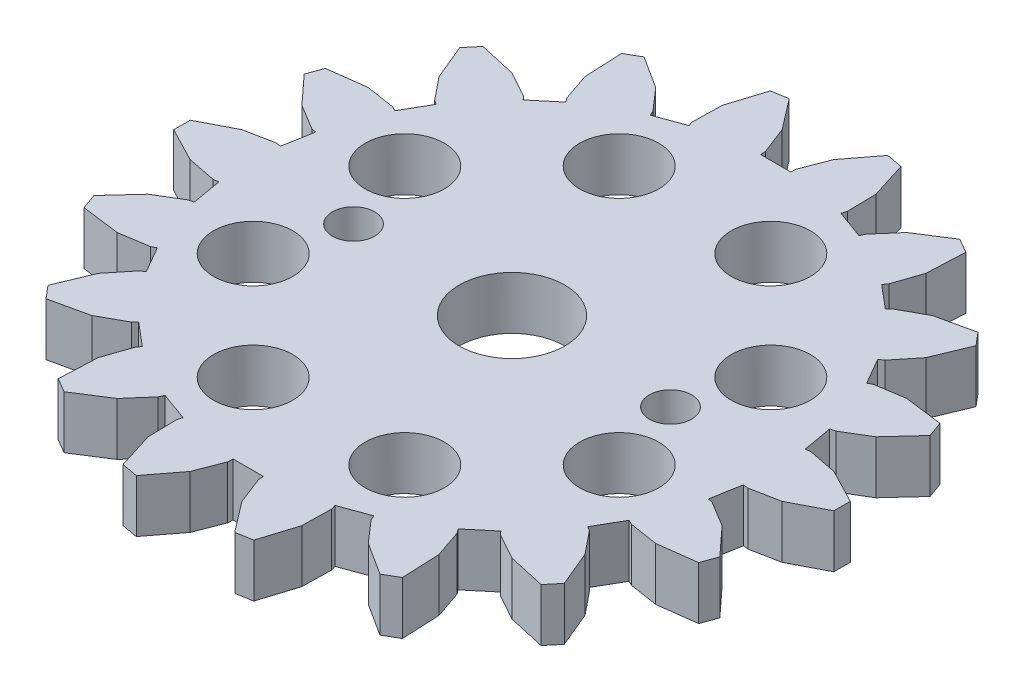
SolidWorks part; units mm, degrees
material "Acrylic (Medium-high impact)"
ref_plane "Front Plane" through (0, 0, 0) normal (0, 0, 1) x (1, 0, 0)
ref_plane "Top Plane" through (0, 0, 0) normal (0, 1, 0) x (1, 0, 0)
ref_plane "Right Plane" through (0, 0, 0) normal (1, 0, 0) x (0, 0, -1)
sketch "Sketch2" plane through (0, 0, 0) normal (0, 1, 0) x (1, 0, 0)
  line L0 (47.7625, 28.9478) -> (48.1516, 28.9935)
  line L1 (48.1516, 28.9935) -> (50.3142, 28.5692)
  line L2 (50.3142, 28.5692) -> (52.8918, 27.2307)
  line L3 (52.8918, 27.2307) -> (52.8918, 25.9859)
  line L4 (52.8918, 25.9859) -> (50.3142, 24.6474)
  line L5 (50.3142, 24.6474) -> (48.1516, 24.2231)
  line L6 (48.1516, 24.2231) -> (47.7625, 24.2688)
  line L7 (47.7625, 24.2688) -> (47.3647, 22.0134)
  line L8 (47.3647, 22.0134) -> (47.7462, 21.9233)
  line L9 (47.7462, 21.9233) -> (49.6331, 20.785)
  line L10 (49.6331, 20.785) -> (51.5977, 18.6455)
  line L11 (51.5977, 18.6455) -> (51.1718, 17.4756)
  line L12 (51.1718, 17.4756) -> (48.2916, 17.0996)
  line L13 (48.2916, 17.0996) -> (46.1145, 17.4405)
  line L14 (46.1145, 17.4405) -> (45.7645, 17.6166)
  line L15 (45.7645, 17.6166) -> (44.6194, 15.6331)
  line L16 (44.6194, 15.6331) -> (44.9469, 15.4181)
  line L17 (44.9469, 15.4181) -> (46.3307, 13.703)
  line L18 (46.3307, 13.703) -> (47.4452, 11.0207)
  line L19 (47.4452, 11.0207) -> (46.6449, 10.0669)
  line L20 (46.6449, 10.0669) -> (43.8096, 10.6987)
  line L21 (43.8096, 10.6987) -> (41.8805, 11.7635)
  line L22 (41.8805, 11.7635) -> (41.6117, 12.0488)
  line L23 (41.6117, 12.0488) -> (39.8572, 10.5766)
  line L24 (39.8572, 10.5766) -> (40.0916, 10.2624)
  line L25 (40.0916, 10.2624) -> (40.8053, 8.1776)
  line L26 (40.8053, 8.1776) -> (40.9351, 5.276)
  line L27 (40.9351, 5.276) -> (39.857, 4.6534)
  line L28 (39.857, 4.6534) -> (37.4087, 6.2167)
  line L29 (37.4087, 6.2167) -> (35.9601, 7.8772)
  line L30 (35.9601, 7.8772) -> (35.8052, 8.2373)
  line L31 (35.8052, 8.2373) -> (33.653, 7.4539)
  line L32 (33.653, 7.4539) -> (33.7657, 7.0785)
  line L33 (33.7657, 7.0785) -> (33.7233, 4.8753)
  line L34 (33.7233, 4.8753) -> (32.8529, 2.1042)
  line L35 (32.8529, 2.1042) -> (31.6267, 1.8881)
  line L36 (31.6267, 1.8881) -> (29.861, 4.1942)
  line L37 (29.861, 4.1942) -> (29.0677, 6.2501)
  line L38 (29.0677, 6.2501) -> (29.0452, 6.6414)
  line L39 (29.0452, 6.6414) -> (26.755, 6.6414)
  line L40 (26.755, 6.6414) -> (26.7324, 6.2501)
  line L41 (26.7324, 6.2501) -> (25.9392, 4.1942)
  line L42 (25.9392, 4.1942) -> (24.1734, 1.8881)
  line L43 (24.1734, 1.8881) -> (22.9472, 2.1042)
  line L44 (22.9472, 2.1042) -> (22.0768, 4.8753)
  line L45 (22.0768, 4.8753) -> (22.0344, 7.0785)
  line L46 (22.0344, 7.0785) -> (22.1471, 7.4539)
  line L47 (22.1471, 7.4539) -> (19.995, 8.2373)
  line L48 (19.995, 8.2373) -> (19.84, 7.8772)
  line L49 (19.84, 7.8772) -> (18.3914, 6.2167)
  line L50 (18.3914, 6.2167) -> (15.9432, 4.6534)
  line L51 (15.9432, 4.6534) -> (14.865, 5.276)
  line L52 (14.865, 5.276) -> (14.9948, 8.1776)
  line L53 (14.9948, 8.1776) -> (15.7085, 10.2624)
  line L54 (15.7085, 10.2624) -> (15.943, 10.5766)
  line L55 (15.943, 10.5766) -> (14.1884, 12.0488)
  line L56 (14.1884, 12.0488) -> (13.9196, 11.7635)
  line L57 (13.9196, 11.7635) -> (11.9905, 10.6987)
  line L58 (11.9905, 10.6987) -> (9.1553, 10.0669)
  line L59 (9.1553, 10.0669) -> (8.355, 11.0207)
  line L60 (8.355, 11.0207) -> (9.4694, 13.703)
  line L61 (9.4694, 13.703) -> (10.8533, 15.4181)
  line L62 (10.8533, 15.4181) -> (11.1808, 15.6331)
  line L63 (11.1808, 15.6331) -> (10.0357, 17.6166)
  line L64 (10.0357, 17.6166) -> (9.6856, 17.4405)
  line L65 (9.6856, 17.4405) -> (7.5085, 17.0996)
  line L66 (7.5085, 17.0996) -> (4.6283, 17.4756)
  line L67 (4.6283, 17.4756) -> (4.2024, 18.6455)
  line L68 (4.2024, 18.6455) -> (6.1671, 20.785)
  line L69 (6.1671, 20.785) -> (8.054, 21.9233)
  line L70 (8.054, 21.9233) -> (8.4355, 22.0134)
  line L71 (8.4355, 22.0134) -> (8.0377, 24.2688)
  line L72 (8.0377, 24.2688) -> (7.6485, 24.2231)
  line L73 (7.6485, 24.2231) -> (5.4859, 24.6474)
  line L74 (5.4859, 24.6474) -> (2.9083, 25.9859)
  line L75 (2.9083, 25.9859) -> (2.9083, 27.2307)
  line L76 (2.9083, 27.2307) -> (5.4859, 28.5692)
  line L77 (5.4859, 28.5692) -> (7.6485, 28.9935)
  line L78 (7.6485, 28.9935) -> (8.0377, 28.9478)
  line L79 (8.0377, 28.9478) -> (8.4355, 31.2032)
  line L80 (8.4355, 31.2032) -> (8.054, 31.2933)
  line L81 (8.054, 31.2933) -> (6.1671, 32.4315)
  line L82 (6.1671, 32.4315) -> (4.2024, 34.5711)
  line L83 (4.2024, 34.5711) -> (4.6283, 35.741)
  line L84 (4.6283, 35.741) -> (7.5085, 36.117)
  line L85 (7.5085, 36.117) -> (9.6856, 35.7761)
  line L86 (9.6856, 35.7761) -> (10.0357, 35.6)
  line L87 (10.0357, 35.6) -> (11.1808, 37.5835)
  line L88 (11.1808, 37.5835) -> (10.8533, 37.7985)
  line L89 (10.8533, 37.7985) -> (9.4694, 39.5136)
  line L90 (9.4694, 39.5136) -> (8.355, 42.1959)
  line L91 (8.355, 42.1959) -> (9.1553, 43.1497)
  line L92 (9.1553, 43.1497) -> (11.9905, 42.5179)
  line L93 (11.9905, 42.5179) -> (13.9196, 41.4531)
  line L94 (13.9196, 41.4531) -> (14.1884, 41.1678)
  line L95 (14.1884, 41.1678) -> (15.943, 42.64)
  line L96 (15.943, 42.64) -> (15.7085, 42.9541)
  line L97 (15.7085, 42.9541) -> (14.9948, 45.0389)
  line L98 (14.9948, 45.0389) -> (14.865, 47.9406)
  line L99 (14.865, 47.9406) -> (15.9432, 48.5632)
  line L100 (15.9432, 48.5632) -> (18.3914, 46.9999)
  line L101 (18.3914, 46.9999) -> (19.84, 45.3394)
  line L102 (19.84, 45.3394) -> (19.995, 44.9793)
  line L103 (19.995, 44.9793) -> (22.1471, 45.7627)
  line L104 (22.1471, 45.7627) -> (22.0344, 46.1381)
  line L105 (22.0344, 46.1381) -> (22.0768, 48.3413)
  line L106 (22.0768, 48.3413) -> (22.9472, 51.1123)
  line L107 (22.9472, 51.1123) -> (24.1734, 51.3285)
  line L108 (24.1734, 51.3285) -> (25.9392, 49.0224)
  line L109 (25.9392, 49.0224) -> (26.7324, 46.9665)
  line L110 (26.7324, 46.9665) -> (26.755, 46.5752)
  line L111 (26.755, 46.5752) -> (29.0452, 46.5752)
  line L112 (29.0452, 46.5752) -> (29.0677, 46.9665)
  line L113 (29.0677, 46.9665) -> (29.861, 49.0224)
  line L114 (29.861, 49.0224) -> (31.6267, 51.3285)
  line L115 (31.6267, 51.3285) -> (32.8529, 51.1123)
  line L116 (32.8529, 51.1123) -> (33.7233, 48.3413)
  line L117 (33.7233, 48.3413) -> (33.7657, 46.1381)
  line L118 (33.7657, 46.1381) -> (33.653, 45.7627)
  line L119 (33.653, 45.7627) -> (35.8052, 44.9793)
  line L120 (35.8052, 44.9793) -> (35.9601, 45.3394)
  line L121 (35.9601, 45.3394) -> (37.4087, 46.9999)
  line L122 (37.4087, 46.9999) -> (39.857, 48.5632)
  line L123 (39.857, 48.5632) -> (40.9351, 47.9406)
  line L124 (40.9351, 47.9406) -> (40.8053, 45.0389)
  line L125 (40.8053, 45.0389) -> (40.0916, 42.9541)
  line L126 (40.0916, 42.9541) -> (39.8572, 42.64)
  line L127 (39.8572, 42.64) -> (41.6117, 41.1678)
  line L128 (41.6117, 41.1678) -> (41.8805, 41.4531)
  line L129 (41.8805, 41.4531) -> (43.8096, 42.5179)
  line L130 (43.8096, 42.5179) -> (46.6449, 43.1497)
  line L131 (46.6449, 43.1497) -> (47.4452, 42.1959)
  line L132 (47.4452, 42.1959) -> (46.3307, 39.5136)
  line L133 (46.3307, 39.5136) -> (44.9469, 37.7985)
  line L134 (44.9469, 37.7985) -> (44.6194, 37.5835)
  line L135 (44.6194, 37.5835) -> (45.7645, 35.6)
  line L136 (45.7645, 35.6) -> (46.1145, 35.7761)
  line L137 (46.1145, 35.7761) -> (48.2916, 36.117)
  line L138 (48.2916, 36.117) -> (51.1718, 35.741)
  line L139 (51.1718, 35.741) -> (51.5977, 34.5711)
  line L140 (51.5977, 34.5711) -> (49.6331, 32.4315)
  line L141 (49.6331, 32.4315) -> (47.7462, 31.2933)
  line L142 (47.7462, 31.2933) -> (47.3647, 31.2032)
  line L143 (47.3647, 31.2032) -> (47.7625, 28.9478)
  line L144 (27.9001, 46.5752) -> (27.9001, 6.6414) construction
  line L145 (52.8918, 26.6083) -> (2.9083, 26.6083) construction
sketch "Sketch3" plane through (0, 0, 0) normal (0, 1, 0) x (1, 0, 0)
  line L0 (27.9001, 46.5752) -> (27.9001, 6.6414) construction
  line L1 (15.9001, 26.6083) -> (39.9001, 26.6083) construction
  line L2 (52.8918, 26.6083) -> (2.9083, 26.6083) construction
  line L3 (27.9001, 32.1459) -> (27.9001, 5.7347) construction
  circle A0 centre (27.9001, 26.6083) radius 4
  circle A1 centre (15.9001, 26.6083) radius 1.6
  circle A2 centre (39.9001, 26.6083) radius 1.6
  point P11 (27.9001, 26.6083)
  dimension "D1" = 8
  dimension "D2" = 3.2
  dimension "D3" = 12
extrude "Boss-Extrude1" add sketch "Sketch2" along normal blind 4
extrude "Cut-Extrude1" cut sketch "Sketch3" along normal up to next
sketch "Sketch4" plane through (0, 0, 0) normal (0, 1, 0) x (1, 0, 0)
  line L0 (27.9001, 26.6083) -> (2.9083, 26.6083) construction
  line L1 (2.9083, 27.2307) -> (2.9083, 25.9859) construction
  line L2 (27.9001, 26.6083) -> (-0.6364, 38.4285) construction
  circle A0 centre (14.0419, 32.3485) radius 3
  point P0 (27.9001, 26.6083)
  dimension "D3" = 6
  dimension "D1" = 22.5
  dimension "D2" = 15
extrude "Cut-Extrude2" cut sketch "Sketch4" along normal up to next
pattern_circular "CirPattern1" count 8 over 360 about axis through (27.9001, 4, -26.6083) along (0, -1, 0) of "Cut-Extrude2"
